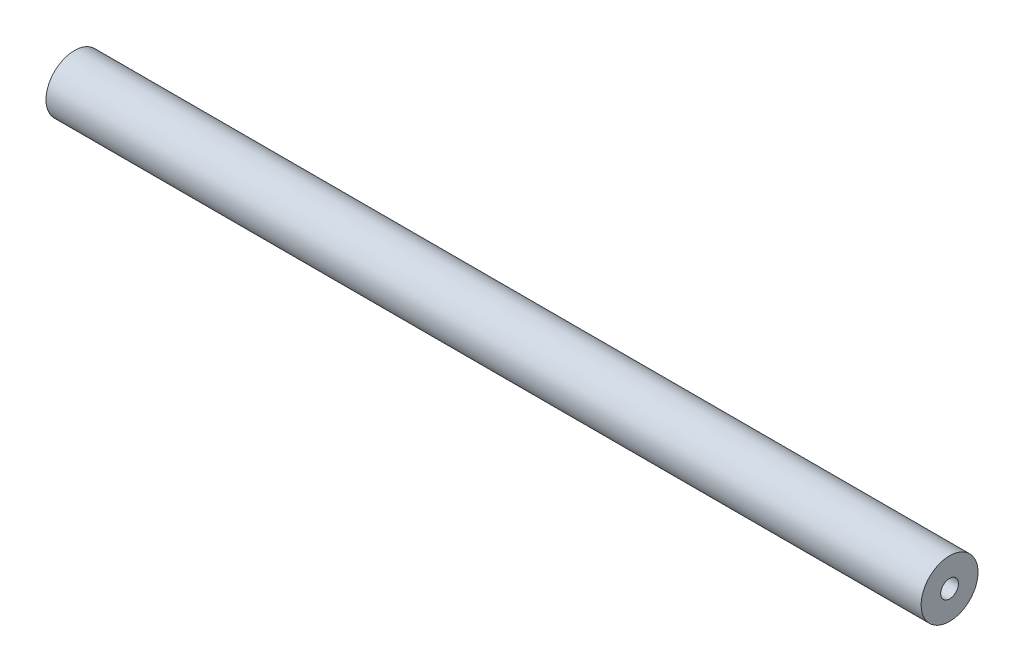
SolidWorks part; units mm, degrees
material "6061 합금"
ref_plane "정면" through (0, 0, 0) normal (0, 0, 1) x (1, 0, 0)
ref_plane "윗면" through (0, 0, 0) normal (0, 1, 0) x (1, 0, 0)
ref_plane "우측면" through (0, 0, 0) normal (1, 0, 0) x (0, 0, -1)
sketch "스케치2" plane through (0, 0, 0) normal (1, 0, 0) x (0, 0, -1)
  circle A0 centre (0, 0) radius 4
  dimension "D1" = 8
extrude "보스-돌출1" add sketch "스케치2" along normal up to surface (61.4968 mm away)
hole_wizard "M3x0.5 나사 구멍1" positions "스케치3" profile "스케치4" tap size "M3x0.5" standard "Ansi Metric"
sketch "스케치3" plane through (61.4968, 0, 0) normal (1, 0, 0) x (0, 0, -1)
  point P0 (0, 0)
sketch "스케치4" plane through (61.4968, 0, 0) normal (0, 1, 0) x (0, 0, -1)
  line L0 (0, 0) -> (0, 22.2511)
  line L1 (0, 22.2511) -> (1.25, 21.5)
  line L2 (1.25, 21.5) -> (1.25, 0)
  line L5 (1.25, 0) -> (0, 0)
  line L10 (0, 22.2511) -> (-1.25, 21.5) construction
  line L11 (0, -6.35) -> (0, 107.95) construction
  dimension "탭 드릴 지름" = 2.5
  dimension "탭 드릴 깊이" = 21.5
  dimension "드릴 각도" = 118
cosmetic thread "구멍 나사산1"
mirror "대칭 복사1" about plane through (0, 0, 0) normal (1, 0, 0) of "M3x0.5 나사 구멍1", "보스-돌출1"
